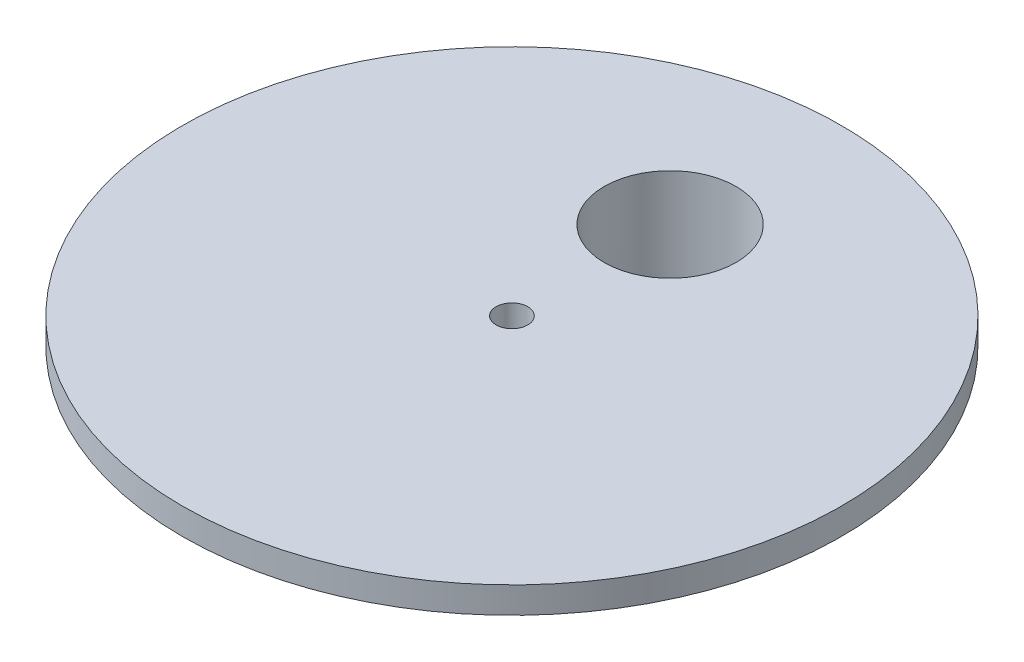
SolidWorks part; units mm, degrees
material "1060-H12"
ref_plane "Front" through (0, 0, 0) normal (0, 0, 1) x (1, 0, 0)
ref_plane "Top" through (0, 0, 0) normal (0, 1, 0) x (1, 0, 0)
ref_plane "Right" through (0, 0, 0) normal (1, 0, 0) x (0, 0, -1)
sketch "Sketch1" plane through (0, 0, 0) normal (0, 1, 0) x (1, 0, 0)
  line L0 (0, 0) -> (0, 125) construction
  circle A0 centre (0, 0) radius 125
  circle A1 centre (0, 60) radius 25
  circle A2 centre (0, 0) radius 6
  dimension "D1" = 250
  dimension "D2" = 12
  dimension "D3" = 50
  dimension "D4" = 60
extrude "Boss-Extrude1" add sketch "Sketch1" along normal blind 10
sketch "Sketch2" plane through (0, 0, 0) normal (0, -1, 0) x (1, 0, 0)
  circle A0 centre (0, -60) radius 25
  circle A1 centre (0, -60) radius 30
  dimension "D2" = 60
  dimension "D1" = 5
extrude "Boss-Extrude2" add sketch "Sketch2" along normal blind 50
